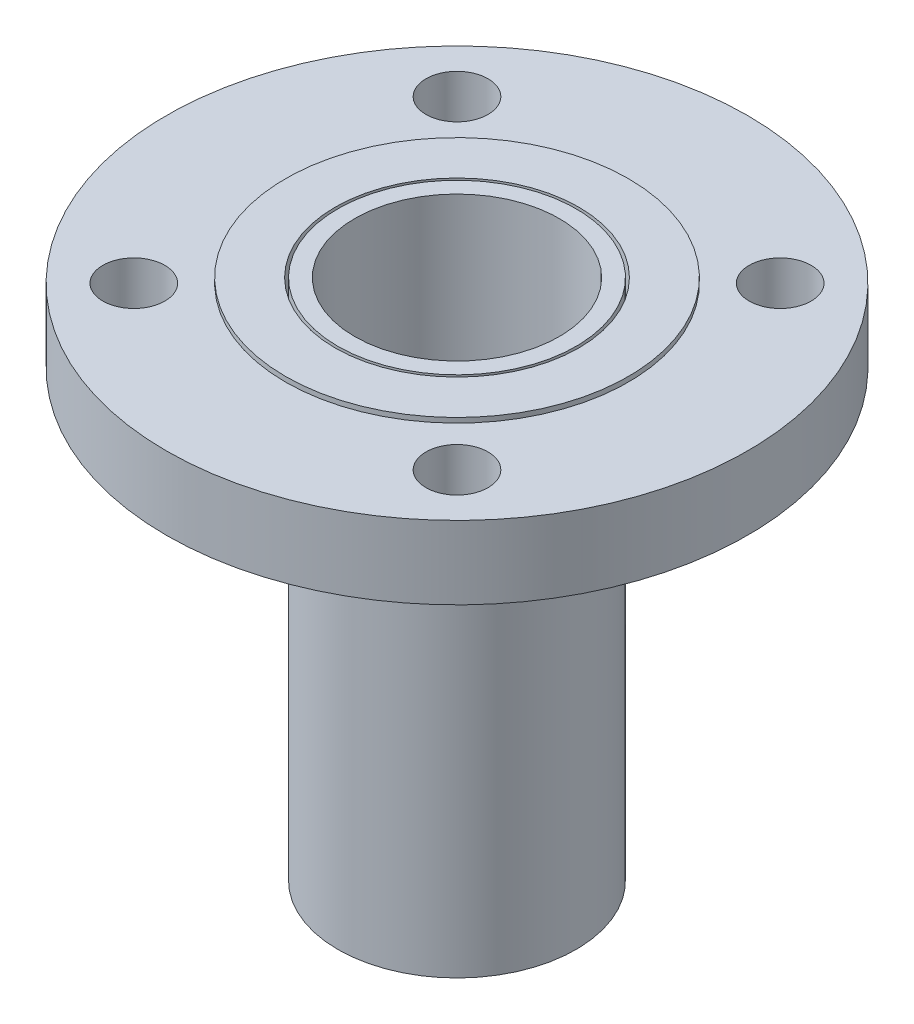
SolidWorks part; units mm, degrees
ref_plane "Front Plane" through (0, 0, 0) normal (0, 0, 1) x (1, 0, 0)
ref_plane "Top Plane" through (0, 0, 0) normal (0, 1, 0) x (1, 0, 0)
ref_plane "Right Plane" through (0, 0, 0) normal (1, 0, 0) x (0, 0, -1)
sketch "Sketch1" plane through (0, 0, 0) normal (0, 1, 0) x (1, 0, 0)
  line L0 (0, 0) -> (-50000, 0) construction
  line L1 (0, 0) -> (0, 50000) construction
  circle A0 centre (0, 0) radius 89
  circle A1 centre (0, 0) radius 37.35
  circle A2 centre (0, 0) radius 70 construction
  circle A3 centre (-49.4975, 49.4975) radius 9.5
  circle A4 centre (-49.4975, -49.4975) radius 9.5
  circle A5 centre (49.4975, -49.4975) radius 9.5
  circle A6 centre (49.4975, 49.4975) radius 9.5
  dimension "D1" = 178
  dimension "D2" = 74.7
  dimension "D3" = 140
  dimension "D5" = 19
extrude "Boss-Extrude1" add sketch "Sketch1" along normal blind 22.4
sketch "Sketch2" plane through (0, 22.4, 0) normal (0, 1, 0) x (1, 0, 0)
  circle A0 centre (0, 0) radius 52.5
  circle A1 centre (0, 0) radius 37.35
  dimension "D1" = 105
extrude "Boss-Extrude2" add sketch "Sketch2" along normal blind 1.5
sketch "Sketch3" plane through (0, 23.9, 0) normal (0, 1, 0) x (1, 0, 0)
  circle A0 centre (0, 0) radius 36.5
  circle A1 centre (0, 0) radius 31.34
  dimension "D1" = 73
  dimension "D2" = 5.16
extrude "Boss-Extrude3" add sketch "Sketch3" against normal blind 160 separate body
ref_axis "Axis1" through (0, -136.1, 0) along (0, 1, 0)
